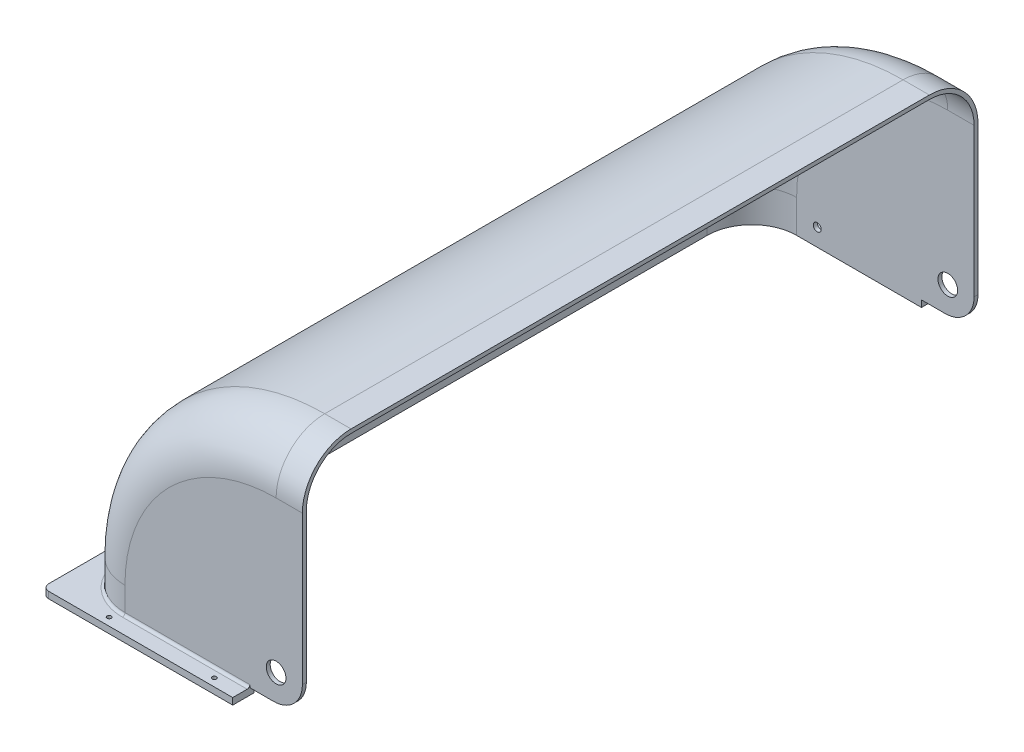
SolidWorks part; units mm, degrees
ref_plane "Front Plane" through (0, 0, 0) normal (0, 0, 1) x (1, 0, 0)
ref_plane "Top Plane" through (0, 0, 0) normal (0, 1, 0) x (1, 0, 0)
ref_plane "Right Plane" through (0, 0, 0) normal (1, 0, 0) x (0, 0, -1)
sketch "Sketch1" plane through (0, 0, 0) normal (0, 1, 0) x (1, 0, 0)
  line L0 (0, -254) -> (0, 254) construction
  line L2 (-165, 270) -> (-165, -270)
  line L5 (-165, 270) -> (0, 0) construction
  line L6 (-165, -270) -> (0, 0) construction
  line L9 (-149, -254) -> (-149, 254)
  line L11 (-149, 254) -> (0, 254)
  line L12 (-165, 270) -> (0, 270)
  line L21 (-149, -254) -> (0, -254)
  line L22 (-165, -270) -> (0, -270)
  line L23 (0, 254) -> (0, 270)
  line L24 (0, -254) -> (0, -270)
  line L25 (0, 270) -> (0, 264) construction
  line L26 (0, 264) -> (-40, 264) construction
  line L27 (-40, 264) -> (-120, 264) construction
  line L28 (-165, 0) -> (-159, 0) construction
  line L29 (-159, 0) -> (-159, 50) construction
  line L30 (-159, 50) -> (-159, 130) construction
  line L31 (0, 0) -> (-149, 0) construction
  line L32 (-159, 210) -> (-159, 50) construction
  line L33 (-40, -264) -> (-120, -264) construction
  line L34 (-159, -210) -> (-159, -50) construction
  line L35 (-159, -50) -> (-159, -130) construction
  circle A0 centre (-159, 130) radius 1.6
  circle A1 centre (-159, 50) radius 1.6
  circle A2 centre (-120, 264) radius 1.6
  circle A3 centre (-40, 264) radius 1.6
  circle A4 centre (-159, 210) radius 1.6
  circle A5 centre (-40, -264) radius 1.6
  circle A6 centre (-120, -264) radius 1.6
  circle A7 centre (-159, -210) radius 1.6
  circle A8 centre (-159, -50) radius 1.6
  circle A9 centre (-159, -130) radius 1.6
  point P0 (0, 0)
  point P9 (0, 0)
  point P26 (-159, 130)
  point P38 (-159, -130)
  dimension "D13" = 80
  dimension "D1" = 16
  dimension "D2" = 540
  dimension "D3" = 16
  dimension "D4" = 16
  dimension "D5" = 165
  dimension "D6" = 165
  dimension "D7" = 6
  dimension "D8" = 80
  dimension "D9" = 40
  dimension "D10" = 6
  dimension "D11" = 50
  dimension "D12" = 80
extrude "Boss-Extrude1" add sketch "Sketch1" along normal blind 5
sketch "Sketch12" plane through (0, 5, 0) normal (0, 1, 0) x (1, 0, 0)
  line L0 (0, -254) -> (-149, -254) construction
  line L1 (0, 254) -> (-149, 254)
  line L2 (0, 254) -> (0, -254) construction
  line L3 (0, -254) -> (-149, -254)
  line L4 (-149, 254) -> (-149, -254)
  line L5 (0, 257) -> (-152, 257)
  line L6 (-152, 257) -> (-152, -257)
  line L7 (0, -257) -> (-152, -257)
  line L8 (0, 257) -> (0, 254)
  line L9 (0, -257) -> (0, -254)
  dimension "D1" = 3
extrude "Boss-Extrude5" add sketch "Sketch12" along normal blind 20
fillet "Fillet8" radius 34 2 edges at (-149, 12.5, 254) (-149, 12.5, -254)
fillet "Fillet9" radius 37 2 edges at (-152, 15, -257) (-152, 15, 257)
sketch "Sketch13" plane through (0, 25, 0) normal (0, 1, 0) x (1, 0, 0)
  line L0 (0, 254) -> (-115, 254)
  line L1 (0, 257) -> (-115, 257)
  line L2 (0, 257) -> (0, -257) construction
  line L3 (0, -257) -> (-115, -257)
  line L4 (-152, 220) -> (-152, -220)
  line L5 (-149, 220) -> (-149, -220)
  line L6 (0, -254) -> (-115, -254)
  line L7 (0, 257) -> (0, 254)
  line L8 (0, -257) -> (0, -254)
  arc A0 (-115, 257) -> (-152, 220) centre (-115, 220) ccw
  arc A1 (-115, -257) -> (-152, -220) centre (-115, -220) cw
  arc A2 (-115, 254) -> (-149, 220) centre (-115, 220) ccw
  arc A3 (-115, -254) -> (-149, -220) centre (-115, -220) cw
  dimension "D3" = 37
  dimension "D4" = 37
  dimension "D1" = 152
  dimension "D2" = 514
  dimension "D5" = 3
revolve "Revolve4" add sketch "Sketch13" angle 90 about L2 reverse direction yes
sketch "Sketch15" plane through (0, 0, 0) normal (1, 0, 0) x (0, 0, -1)
  line L0 (-254, 5) -> (-254, 140)
  line L1 (-257, 5) -> (257, 5) construction
  line L2 (-257, 5) -> (-257, 140)
  line L3 (-220, 177) -> (220, 177)
  line L4 (257, 5) -> (257, 140)
  line L5 (-220, 174) -> (220, 174)
  line L6 (254, 5) -> (254, 140)
  line L7 (-257, 5) -> (-270, 5)
  line L8 (-270, 5) -> (-270, 0)
  line L9 (-270, 0) -> (-254, 0)
  line L10 (-254, 0) -> (-254, 5)
  line L11 (254, 5) -> (254, 0)
  line L12 (254, 0) -> (270, 0)
  line L13 (270, 0) -> (270, 5)
  line L14 (270, 5) -> (257, 5)
  arc A0 (-220, 177) -> (-257, 140) centre (-220, 140) ccw
  arc A1 (257, 140) -> (220, 177) centre (220, 140) ccw
  arc A2 (-220, 174) -> (-254, 140) centre (-220, 140) ccw
  arc A3 (254, 140) -> (220, 174) centre (220, 140) ccw
  dimension "D3" = 37
  dimension "D4" = 37
  dimension "D1" = 514
  dimension "D2" = 172
  dimension "D5" = 3
extrude "Boss-Extrude6" add sketch "Sketch15" along normal blind 20
sketch "Sketch16" plane through (0, 0, 270) normal (0, 0, 1) x (1, 0, 0)
  line L0 (-115, 5) -> (20, 5) construction
  line L1 (20, 0) -> (-20, 0)
  line L2 (20, 0) -> (20, 5)
  line L3 (20, 5) -> (-20, 5)
  line L4 (-20, 0) -> (-20, 5)
  dimension "D1" = 40
  dimension "D2" = 5
extrude "Cut-Extrude3" cut sketch "Sketch16" against normal up to surface (540 mm away) up to face at (-72.5, 2.5, -270)
fillet "Fillet10" radius 22 2 edges at (20, 5, 255.5) (20, 5, -255.5)
sketch "Sketch17" plane through (0, 0, 257) normal (0, 0, 1) x (1, 0, 0)
  line L0 (-115, 25) -> (20, 25) construction
  line L1 (20, 140) -> (20, 27) construction
  line L2 (0, 140) -> (0, 0) construction
  arc A0 (0, 140) -> (-115, 25) centre (0, 25) ccw construction
  circle A1 centre (0, 25) radius 7.5
  dimension "D1" = 25
extrude "Cut-Extrude4" cut sketch "Sketch17" against normal up to surface (514 mm away) up to face at (-33.0373, 52.323, -257)
fillet "Fillet11" radius 5 2 edges at (-165, 2.5, -270) (-165, 2.5, 270)
fillet "Fillet12" radius 2 5 edges at (-67.5, 5, -257) (-141.163, 5, -246.163) (-67.5, 5, 257) (-141.163, 5, 246.163) (-152, 5, 0)
sketch "Sketch18" plane through (0, 0, -257) normal (0, 0, -1) x (-1, 0, 0)
  line L0 (0, 25) -> (152, 7) construction
  line L1 (152, 25) -> (152, 7) construction
  line L2 (115, 7) -> (152, 7) construction
  line L3 (0, 25) -> (99.3061, 13.2401) construction
  circle A0 centre (99.3061, 13.2401) radius 3
  dimension "D2" = 6
  dimension "D1" = 100
extrude "Cut-Extrude5" cut sketch "Sketch18" against normal up to surface (511 mm away) up to face at (7.5, 25, 254)
